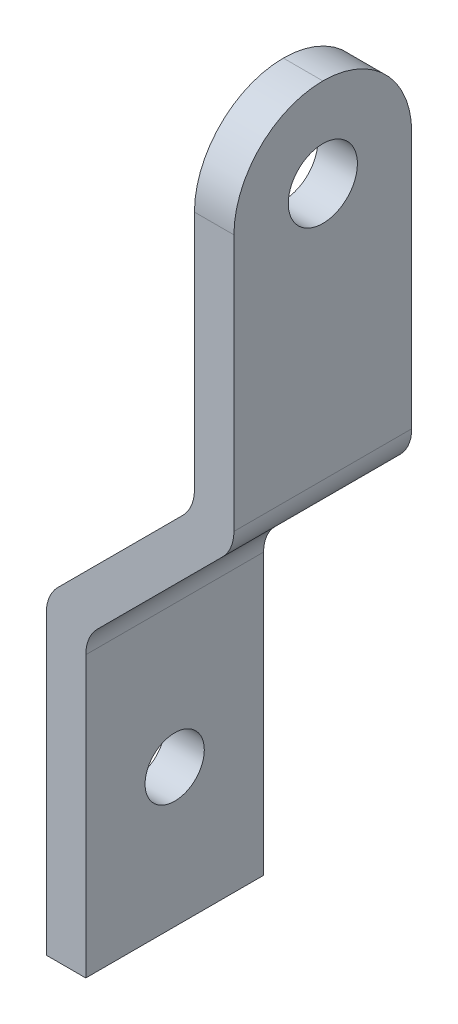
SolidWorks part; units mm, degrees
ref_plane "Front Plane" through (0, 0, 0) normal (0, 0, 1) x (1, 0, 0)
ref_plane "Top Plane" through (0, 0, 0) normal (0, 1, 0) x (1, 0, 0)
ref_plane "Right Plane" through (0, 0, 0) normal (1, 0, 0) x (0, 0, -1)
sketch "Sketch1" plane through (0, 0, 0) normal (0, 0, 1) x (1, 0, 0)
  line L0 (0, 0) -> (0, 20.1021)
  line L1 (0, 20.1021) -> (9.525, 29.6271)
  line L2 (9.525, 29.6271) -> (9.525, 51.8521)
  line L3 (9.525, 51.8521) -> (12.065, 51.8521)
  line L4 (12.065, 51.8521) -> (12.065, 28.575)
  line L5 (12.065, 28.575) -> (2.54, 19.05)
  line L6 (2.54, 19.05) -> (2.54, 0)
  line L7 (0, 0) -> (2.54, 0)
  dimension "D1" = 2.54
  dimension "D2" = 12.065
  dimension "D3" = 2.54
  dimension "D4" = 2.54
  dimension "D5" = 135
  dimension "D6" = 22.225
  dimension "D7" = 19.05
extrude "Boss-Extrude1" add sketch "Sketch1" along normal blind 11.43
fillet "Fillet1" radius 5.715 2 edges at (10.795, 51.8521, 0) (10.795, 51.8521, 11.43)
sketch "Sketch3" plane through (12.065, 0, 0) normal (1, 0, 0) x (0, 0, -1)
  line L0 (-11.43, 0) -> (-11.43, 19.05) construction
  line L2 (-11.43, 0) -> (0, 0) construction
  circle A0 centre (-5.715, 46.1371) radius 2.2225
  circle A1 centre (-5.715, 8.89) radius 1.905
  arc A4 (-5.715, 51.8521) -> (-11.43, 46.1371) centre (-5.715, 46.1371) ccw construction
  dimension "D1" = 4.445
  dimension "D2" = 3.81
  dimension "D3" = 5.715
  dimension "D4" = 8.89
extrude "Cut-Extrude1" cut sketch "Sketch3" against normal blind 12.7
fillet "Fillet2" radius 2.54 4 edges at (2.54, 19.05, 5.715) (9.525, 29.6271, 5.715) (12.065, 28.575, 5.715) (0, 20.1021, 5.715)
